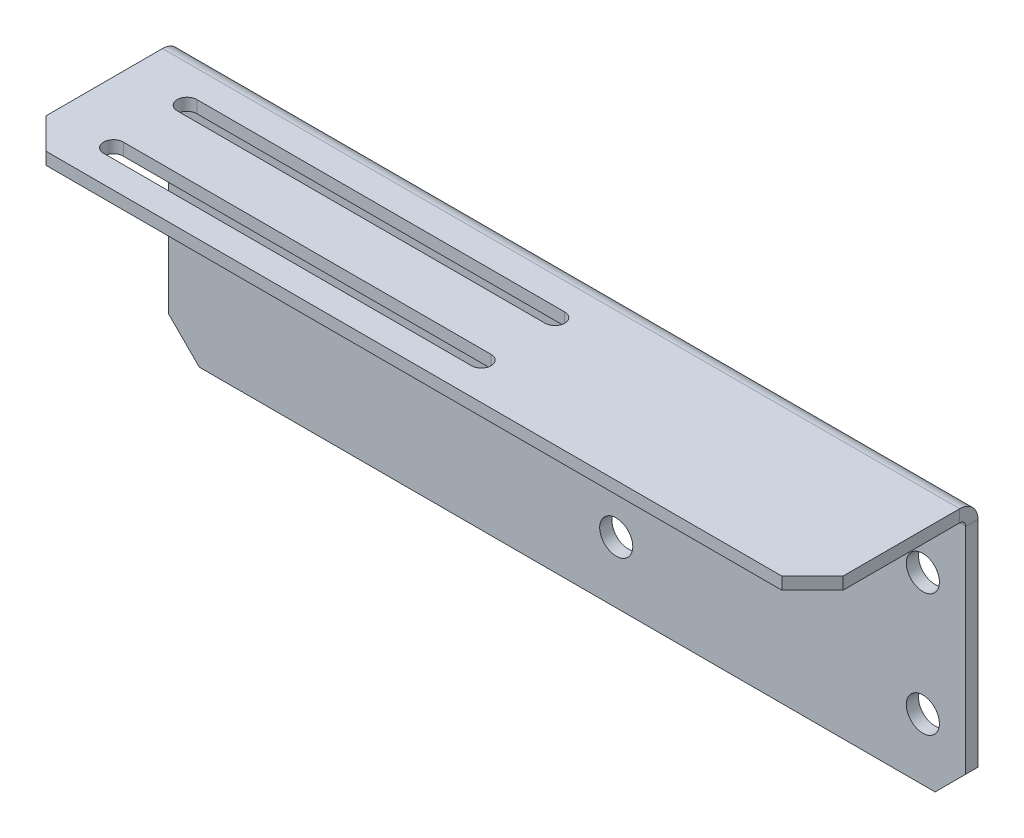
SolidWorks part; units mm, degrees
note: The reader was unsure of these and kept them because the rebuilt part matched: flange length of "邊線-凸緣1".
ref_plane "前基準面" through (0, 0, 0) normal (0, 0, 1) x (1, 0, 0)
ref_plane "上基準面" through (0, 0, 0) normal (0, 1, 0) x (1, 0, 0)
ref_plane "右基準面" through (0, 0, 0) normal (1, 0, 0) x (0, 0, -1)
sketch "草圖17" plane through (0, 0, 0) normal (0, 0, 1) x (1, 0, 0)
  line L0 (0, 19.6137) -> (0, 0) construction
  line L1 (-123, 20) -> (7, 20)
  line L2 (-123, 20) -> (-123, -20)
  line L3 (-123, -20) -> (7, -20)
  line L4 (7, 20) -> (7, -20)
  line L5 (0, 0) -> (11.8281, 0) construction
  dimension "D1" = 40
  dimension "D2" = 7
  dimension "D3" = 130
sheet metal parameters "鈑金1" thickness 2 parameters "D1"=1
base flange "基材-凸緣1" sketch "草圖17" thickness 2 reverse thickness direction yes parameters "D1"=1
hole_wizard "Ø5.4 (5.4) 直徑孔1" positions "草圖13" profile "草圖12" hole size "Ø5.4" standard "ISO" end condition up to next
sketch "草圖13" plane through (-278.0673, 19.1514, 2) normal (0, 0, -1) x (-1, 0, 0)
  line L14 (-285.0673, -19.1514) -> (-284.5444, -19.1514) construction
  line L15 (-285.0673, -39.1514) -> (-285.0673, 0.8486) construction
  point P35 (-228.0673, -29.1514)
  point P37 (-278.0673, -29.1514)
  point P46 (-228.0673, -9.1514)
  point P48 (-278.0673, -9.1514)
  dimension "D1" = 7
  dimension "D2" = 50
  dimension "D3" = 20
sketch "草圖12" plane through (-50, -10, 2) normal (1, 0, 0) x (0, -1, 0)
  line L0 (0, 0) -> (0, 2)
  line L1 (0, 2) -> (2.7, 2)
  line L2 (2.7, 2) -> (2.7, 0)
  line L5 (2.7, 0) -> (0, 0)
  line L11 (0, -6.35) -> (0, 107.95) construction
  dimension "貫穿孔直徑" = 5.4
  dimension "貫穿孔深度" = 2
edge flange "邊線-凸緣1" sketch "草圖21" flange angle 90 flange length 25 flange position bend outside bend radius 1 thickness 2 relief rectangular parameters "D6"=10
sketch "草圖21" plane through (0, 20, 2) normal (0, 1, 0) x (-1, 0, 0)
  line L0 (-7, 0) -> (123, 0) construction
  line L1 (-7, 0) -> (123, 0)
  line L2 (-7, 0) -> (-7, 25)
  line L3 (-7, 25) -> (123, 25)
  line L4 (123, 25) -> (123, 0)
bend "邊線彎折1" bend radius 1 bend angle 90 parameters "D5"=1
sketch "草圖14" plane through (0, 23, 30.5) normal (0, 1, 0) x (1, 0, 0)
  line L0 (-113, 21.5) -> (-53, 21.5) construction
  line L1 (-113, 9.5) -> (-53, 9.5) construction
  line L2 (-83, 21.5) -> (-83, 9.5) construction
  line L3 (-113, 19.9) -> (-53, 19.9)
  line L4 (-113, 23.1) -> (-53, 23.1)
  line L5 (-113, 7.9) -> (-53, 7.9)
  line L6 (-113, 11.1) -> (-53, 11.1)
  line L11 (-123, 3.5) -> (7, 3.5) construction
  line L13 (-123, 27.5) -> (-123, 3.5) construction
  arc A0 (-113, 19.9) -> (-113, 23.1) centre (-113, 21.5) cw
  arc A1 (-53, 19.9) -> (-53, 23.1) centre (-53, 21.5) ccw
  arc A2 (-113, 7.9) -> (-113, 11.1) centre (-113, 9.5) cw
  arc A3 (-53, 7.9) -> (-53, 11.1) centre (-53, 9.5) ccw
  dimension "D8" = 10
  dimension "D2" = 6
  dimension "D7" = 60
  dimension "D1" = 12
  dimension "D3" = 1.6
  dimension "D4" = 1.6
  dimension "D5" = 1.6
  dimension "D6" = 1.6
extrude "除料-伸長4" cut sketch "草圖14" against normal up to next normal cut yes
chamfer "導角1" distance 5 angle 45 4 edges at (7, 22, 27) (-123, 22, 27) (-123, -20, 1) (7, -20, 1)
flat pattern "平板-型式1" [suppressed]
sketch "彎折-線1" plane through (0, 0, 0) normal (0, 1, 0) x (-1, 0, 0)
bend of the flat pattern "平板-<邊線彎折1>1"
